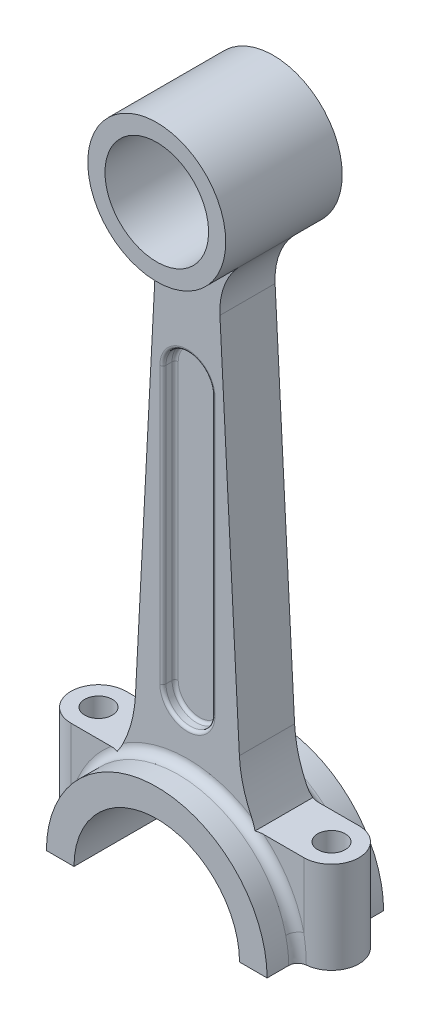
SolidWorks part; units mm, degrees
ref_plane "Front Plane" through (0, 0, 0) normal (0, 0, 1) x (1, 0, 0)
ref_plane "Top Plane" through (0, 0, 0) normal (0, 1, 0) x (1, 0, 0)
ref_plane "Right Plane" through (0, 0, 0) normal (1, 0, 0) x (0, 0, -1)
sketch "Sketch1" plane through (0, 0, 0) normal (0, 0, 1) x (1, 0, 0)
  line L0 (0, 0) -> (0, -5110.48) construction
  line L1 (-254, -511.9534) -> (-453.3823, -4316.3945)
  line L2 (254, -511.9534) -> (453.3823, -4316.3945)
  line L3 (-914.4, -5110.48) -> (-685.8, -5110.48)
  line L4 (914.4, -5110.48) -> (1195.9502, -4977.7704)
  line L5 (685.8, -5110.48) -> (914.4, -5110.48)
  circle A0 centre (0, 0) radius 571.5
  circle A1 centre (0, 0) radius 429.26
  arc A2 (685.8, -5110.48) -> (-685.8, -5110.48) centre (0, -5110.48) ccw
  arc A3 (914.4, -5110.48) -> (-914.4, -5110.48) centre (0, -5110.48) ccw
  point P13 (0, 0)
  dimension "D1" = 1143
  dimension "D2" = 858.52
  dimension "D3" = 1371.6
  dimension "D4" = 1828.8
  dimension "D5" = 5110.48
  dimension "D6" = 508
  dimension "D7" = 6
extrude "Boss-Extrude1" add sketch "Sketch1" along normal mid plane 965.2 contours A1 A0 | A3 A2 | L0 A3 L3 A2 region at (-126.7538, -540.6765, 0) region at (512.8245, -4597.6555, 0) region at (-512.8245, -4597.6555, 0)
extrude "Boss-Extrude2" add sketch "Sketch1<3>" along normal mid plane 457.2 contours A0 L0 A3 L2 | L0 A0 L1 A3 region at (182.482, -2561.475, 0) region at (-182.482, -2561.475, 0)
sketch "Sketch1<3>" plane through (0, 0, 0) normal (0, 0, 1) x (1, 0, 0) same geometry as "Sketch1"
sketch "Sketch2" plane through (0, 0, 228.6) normal (0, 0, 1) x (1, 0, 0)
  line L0 (0, 0) -> (0, -5110.48) construction
  line L1 (0, -3698.24) -> (0, -1412.24) construction
  line L2 (-203.2, -3698.24) -> (-203.2, -1412.24)
  line L3 (203.2, -3698.24) -> (203.2, -1412.24)
  arc A0 (-203.2, -3698.24) -> (203.2, -3698.24) centre (0, -3698.24) ccw
  arc A1 (203.2, -1412.24) -> (-203.2, -1412.24) centre (0, -1412.24) ccw
  point P6 (0, -2555.24)
  dimension "D2" = 203.2
  dimension "D1" = 2286
extrude "Cut-Extrude1" cut sketch "Sketch2" against normal blind 101.6
mirror "Mirror1" about plane through (0, 0, 0) normal (0, 0, 1) of "Cut-Extrude1"
fillet "Fillet1" radius 25.4 16 edges at (-203.2, -2555.24, -127) (0, -1209.04, -127) (203.2, -2555.24, -127) (-203.2, -2555.24, 127) (0, -1209.04, 127) (203.2, -2555.24, 127) (0, -1209.04, 228.6) (203.2, -2555.24, 228.6) (0, -3901.44, 228.6) (0, -1209.04, -228.6) (203.2, -2555.24, -228.6) (0, -3901.44, -228.6) (0, -3901.44, -127) (0, -3901.44, 127) (-203.2, -2555.24, 228.6) (-203.2, -2555.24, -228.6)
ref_plane "Plane1" through (0, -4348.48, 0) normal (0, -1, 0) x (-1, 0, 0)
fillet "Fillet4" radius 1016 2 edges at (-453.3823, -4316.3945, 0) (453.3823, -4316.3945, 0)
sketch "Sketch3" plane through (0, -4348.48, 0) normal (0, -1, 0) x (-1, 0, 0)
  line L0 (965.2, 0) -> (-965.2, 0) construction
  line L1 (965.2, -228.6) -> (-965.2, -228.6)
  line L2 (965.2, 228.6) -> (-965.2, 228.6)
  arc A0 (965.2, -228.6) -> (965.2, 228.6) centre (965.2, 0) ccw
  arc A1 (-965.2, 228.6) -> (-965.2, -228.6) centre (-965.2, 0) ccw
  point P2 (0, 0)
  dimension "D2" = 228.6
  dimension "D1" = 1930.4
extrude "Boss-Extrude3" add sketch "Sketch3" along normal up to surface (762 mm away) up to face at (-800.1, -5110.48, 0)
sketch "Sketch4" plane through (0, 0, 228.6) normal (0, 0, 1) x (1, 0, 0)
  line L1 (-685.8, -5110.48) -> (685.8, -5110.48)
  line L2 (-685.8, -5110.48) -> (685.8, -5110.48)
  arc A1 (685.8, -5110.48) -> (-685.8, -5110.48) centre (0, -5110.48) ccw
  arc A2 (685.8, -5110.48) -> (-685.8, -5110.48) centre (0, -5110.48) ccw
  dimension "D1" = 0
extrude "Cut-Extrude2" cut sketch "Sketch4" against normal through all
sketch "Sketch5" plane through (0, -4348.48, 0) normal (0, 1, 0) x (1, 0, 0)
  circle A0 centre (-965.2, 0) radius 114.3
  circle A1 centre (965.2, 0) radius 114.3
  dimension "D1" = 228.6
  dimension "D2" = 228.6
extrude "Cut-Extrude3" cut sketch "Sketch5" against normal through all
fillet "Fillet3" radius 571.5 2 edges at (254, -511.9534, 0) (-254, -511.9534, 0)
fillet "Fillet5" radius 76.2 2 edges at (0, -4196.08, -228.6) (0, -4196.08, 228.6)
